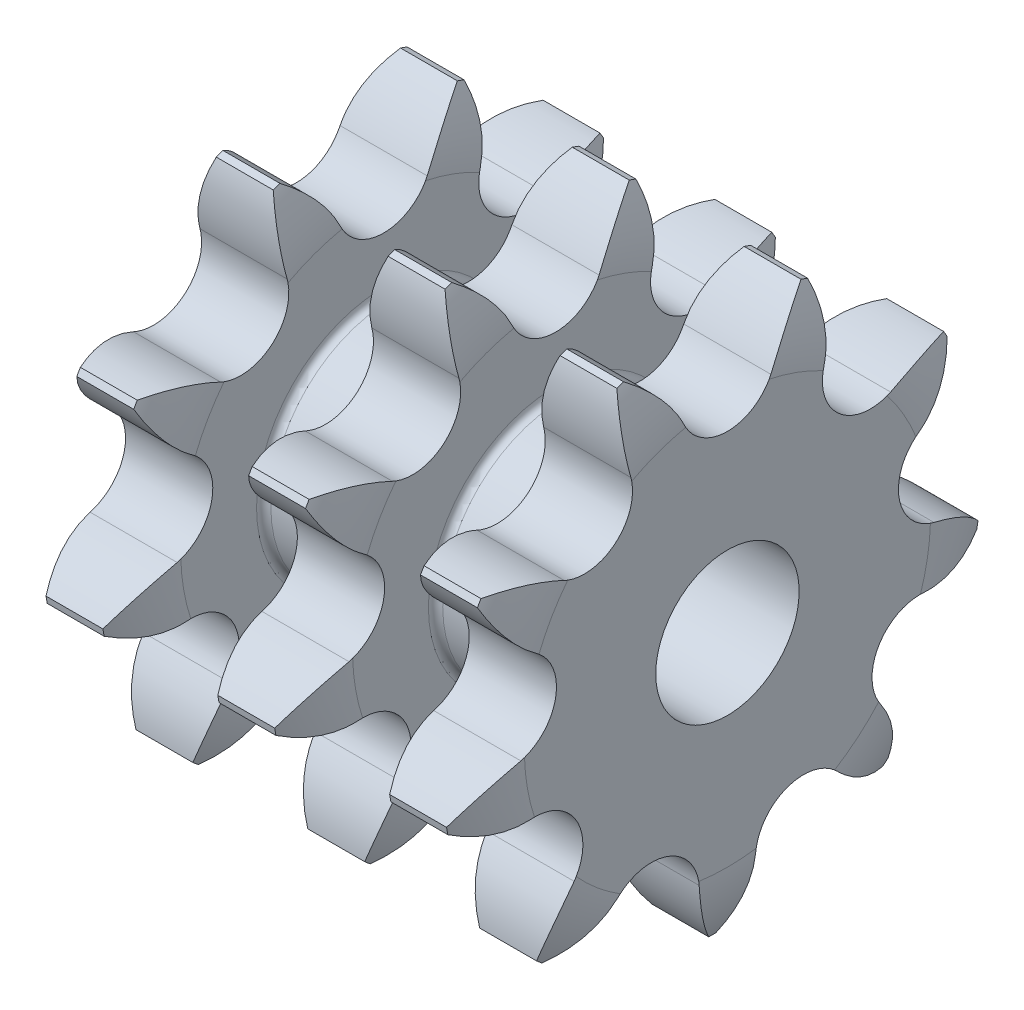
SolidWorks part; units mm, degrees
ref_plane "Plane1" through (0, 0, 0) normal (0, 0, 1) x (1, 0, 0)
ref_plane "Plane2" through (0, 0, 0) normal (0, 1, 0) x (1, 0, 0)
ref_plane "Plane3" through (0, 0, 0) normal (1, 0, 0) x (0, 0, -1)
sketch "Clipboard" plane through (0, 0, 0) normal (0, 1, 0) x (1, 0, 0)
  line L0 (0, 0) -> (12.5436, -1.9867)
  line L1 (-15, 0) -> (100, 0) construction
  line L2 (0, 0) -> (-0.8416, 0.9512)
  line L3 (0, 0) -> (-11.863, 4.5341)
  line L4 (0, 0) -> (3.0618, 0.4849)
  line L5 (0, 0) -> (-2.8109, -1.0484)
  line L6 (0, 0) -> (-29.8924, -20.1685)
  line L7 (-0.8416, 0.9512) -> (36.5829, 8.906)
  line L8 (-76.2, 38.1) -> (-75.2, 38.1)
  line L9 (-73.4321, 41.7084) -> (-72.837, 41.7846)
  line L10 (-73.4741, 12.9512) -> (-59.0941, 12.9512)
  circle A0 centre (0, 0) radius 3.975
  circle A1 centre (0, 0) radius 10.0465
  circle A2 centre (0, 0) radius 25
  dimension "Num_teeth" = 9
  dimension "Thickness" = 36.06
  dimension "Fillet_rad" = 0.6
sketch "BasProSke" plane through (0, 0, 0) normal (0, 1, 0) x (1, 0, 0)
  line L0 (-10, 0) -> (60, 0) construction
  line L1 (0, 0) -> (0, 16.9929)
  line L2 (0, 0) -> (36.06, 0)
  line L3 (36.06, 0) -> (36.06, 16.9929)
  line L4 (34.79, 22.5287) -> (1.27, 22.5287)
  arc A0 (0, 16.9929) -> (1.27, 22.5287) centre (12.7, 16.9929) cw
  arc A1 (36.06, 16.9929) -> (34.79, 22.5287) centre (23.36, 16.9929) ccw
  dimension "D1" = 12.7
  dimension "Thickness" = 36.06
  dimension "Diameter" = 45.0573
  dimension "G1" = 1.27
revolve "Base-Revolve" add sketch "BasProSke" angle 360 about L0
sketch "GrvSke" plane through (0, 0, 0) normal (0, 1, 0) x (1, 0, 0)
  line L0 (7.3, 16.9929) -> (7.3, 10.6465)
  line L1 (7.9, 10.0465) -> (13.78, 10.0465)
  line L2 (14.38, 10.6465) -> (14.38, 16.9929)
  line L3 (6.03, 22.5287) -> (15.65, 22.5287)
  line L4 (10.84, 0) -> (10.84, 52.07) construction
  line L5 (-10, 0) -> (60, 0) construction
  line L6 (0, 0) -> (35.56, 0) construction
  arc A0 (14.38, 16.9929) -> (15.65, 22.5287) centre (27.08, 16.9929) cw
  arc A1 (7.3, 16.9929) -> (6.03, 22.5287) centre (-5.4, 16.9929) ccw
  arc A2 (7.3, 10.6465) -> (7.9, 10.0465) centre (7.9, 10.6465) ccw
  arc A3 (13.78, 10.0465) -> (14.38, 10.6465) centre (13.78, 10.6465) ccw
  dimension "D1" = 12.7
  dimension "Diameter" = 45.0573
  dimension "Fillet_rad" = 0.6
  dimension "G1" = 1.27
  dimension "Grv_width" = 7.08
revolve "Groove" cut sketch "GrvSke" angle 360 about L6
pattern_linear "Grooves" count 2 spacing 14.38 along (1, 0, 0) of "Groove"
sketch "TooCutSke" plane through (0, 0, 0) normal (1, 0, 0) x (0, 0, -1)
  line L0 (0, 18.6059) -> (3.6386, 16.9092) construction
  line L1 (0, 0) -> (0, 107) construction
  line L2 (0, 18.6059) -> (-10, 18.6059) construction
  line L3 (0, 18.6059) -> (-3.6386, 16.9092) construction
  arc A0 (3.6386, 16.9092) -> (7.9748, 21.6037) centre (13.1494, 12.4742) cw
  arc A1 (3.6386, 16.9092) -> (-3.6386, 16.9092) centre (0, 18.6059) cw
  arc A2 (-3.6386, 16.9092) -> (-7.9748, 21.6037) centre (-13.1494, 12.4742) ccw
  arc A3 (7.9748, 21.6037) -> (-7.9748, 21.6037) centre (0, 0) ccw
extrude "ToothCut" cut sketch "TooCutSke" along normal through all
pattern_circular "TeethCuts" count 9 every 40 about axis through (-10, 0, 0) along (1, 0, 0) of "ToothCut"
sketch "HubNeaOneSke" plane through (0, 0, 0) normal (-1, 0, 0) x (0, 0, 1)
  circle A0 centre (0, 0) radius 10.0465
  dimension "Diameter" = 20.093
extrude "HubNearOne" [suppressed] add sketch "HubNeaOneSke" along normal blind 2.2005
fillet "HubNearOneFillet" [suppressed] radius 0.6
sketch "HubNeaBotSke" plane through (0, 0, 0) normal (-1, 0, 0) x (0, 0, 1)
  circle A0 centre (0, 0) radius 10.0465
  dimension "Diameter" = 20.093
extrude "HubNearBoth" [suppressed] add sketch "HubNeaBotSke" along normal blind 1.1003
fillet "HubNearBothFillet" [suppressed] radius 0.6
ref_plane "FarPln" through (36.06, 0, 0) normal (1, 0, 0) x (0, 0, -1)
sketch "HubFarSke" plane through (36.06, 0, 0) normal (1, 0, 0) x (0, 0, -1)
  circle A0 centre (0, 0) radius 10.0465
  dimension "Diameter" = 20.093
extrude "HubFar" [suppressed] add sketch "HubFarSke" along normal blind 1.1003
fillet "HubFarFillet" [suppressed] radius 0.6
sketch "BorSke" plane through (0, 0, 0) normal (1, 0, 0) x (0, 0, -1)
  circle A0 centre (0, 0) radius 6
  dimension "Diameter" = 12
extrude "Bore" cut sketch "BorSke" along normal mid plane 76.521
sketch "KeySke" plane through (0, 0, 0) normal (1, 0, 0) x (0, 0, -1)
  line L0 (-1, 0) -> (-1, 7)
  line L1 (-1, 7) -> (1, 7)
  line L2 (1, 7) -> (1, 0)
  line L3 (0, 0) -> (0, 34) construction
  line L4 (-1, 0) -> (1, 0)
  dimension "Offset" = 7
  dimension "Width" = 2
extrude "Keyway" [suppressed] cut sketch "KeySke" along normal mid plane 76.521
pattern_circular "Keyway2" [suppressed] count 2 every 90 about axis through (-10, 0, 0) along (1, 0, 0) reverse direction yes
equation "' \"Pitch@Clipboard\" = 12.7"
equation "' \"Num_strands@Clipboard\" = 3"
equation "' \"Num_teeth@Clipboard\" = 9"
equation "' \"Hub_dia@Clipboard\" = 50"
equation "' \"Overall_len@Clipboard\" = 3"
equation "' \"Diameter@BorSke\" = 12"
equation "' \"T_dim@Clipboard\" = 1"
equation "' \"Width@KeySke\" = 2"
equation "' \"Dr@Clipboard\" = 7.95"
equation "' \"Face_width@Clipboard\" = 7.3"
equation "' \"Side_radius@Clipboard\" = 12.7"
equation "' \"Side_relief@Clipboard\" = 1.27"
equation "' \"Transv_pitch@Clipboard\" = 14.38"
equation "' \"Show_teeth@Clipboard\" = 9"
equation "' \"Fillet_rad@Clipboard\" = 0.6"
equation "' \"Plate_wid@Clipboard\" = 12"
equation "\"Num_teeth@Clipboard\" = int( \"Num_teeth@Clipboard\" )"
equation "\"Num_teeth@Clipboard\" = ((sgn( \"Num_teeth@Clipboard\" - 5.0)+1)*( \"Num_teeth@Clipboard\" - 5.0))/2 +5.0"
equation "\"Num_teeth@Clipboard\" = ((sgn( \"Num_teeth@Clipboard\" - 200.0)-1)*( \"Num_teeth@Clipboard\" - 200.0))/-2 +200.0"
equation "\"MHD@Clipboard\" = \"Pitch@Clipboard\" * (1.0 / tan(3.14159265 / \"Num_teeth@Clipboard\" )) - 1.05 * \"Plate_wid@Clipboard\" - 2.0 * \"Fillet_rad@Clipboard\" - 1.0"
equation "\"Thickness@Clipboard\"  = \"Face_width@Clipboard\" + (\"Num_strands@Clipboard\" - 1) * \"Transv_pitch@Clipboard\""
equation "\"OAL@Clipboard\" = \"Thickness@Clipboard\" + 2 * \"Fillet_rad@Clipboard\" + 1"
equation "\"MHD@Clipboard\" = ((sgn( \"MHD@Clipboard\" - \"Hub_dia@Clipboard\" )-1)*( \"MHD@Clipboard\" - \"Hub_dia@Clipboard\" ))/-2+ \"Hub_dia@Clipboard\""
equation "\"OAL@Clipboard\" = ((sgn( \"OAL@Clipboard\" - \"Overall_len@Clipboard\" )+1)*( \"OAL@Clipboard\" - \"Overall_len@Clipboard\" ))/2 + \"Overall_len@Clipboard\" + 0.0005"
equation "\"Num_teeth@TeethCuts\" = int( \"Show_teeth@Clipboard\" ) + 1"
equation "\"Num_teeth@TeethCuts\" = ((sgn( \"Num_teeth@TeethCuts\" - \"Num_teeth@Clipboard\" )-1)*( \"Num_teeth@TeethCuts\" - \"Num_teeth@Clipboard\" ))/-2+ \"Num_teeth@Clipboard\""
equation "\"Num_teeth@TeethCuts\" = ((sgn( \"Num_teeth@TeethCuts\" - 2.0)+1)*( \"Num_teeth@TeethCuts\" - 2.0))/2 +2.0"
equation "\"Angle@TeethCuts\" = 360.0 / \"Num_teeth@Clipboard\""
equation "\"Seat_radius@TooCutSke\" = ( \"Pitch@Clipboard\" / 2.0) / sin(3.14159265 / \"Num_teeth@Clipboard\" ) - \"Dr@Clipboard\" / 2.0 + \"Dr@Clipboard\" * 0.505"
equation "\"R1@TooCutSke\"  = \"Dr@Clipboard\" * 0.505"
equation "\"X@TooCutSke\" = 140.0 - (90.0 / \"Num_teeth@Clipboard\")"
equation "\"R2@TooCutSke\" = 0.12 * \"Dr@Clipboard\" * ( \"Num_teeth@Clipboard\" + 2.0)"
equation "\"Overcut@TooCutSke\" = 0.5 + 0.625 * \"Pitch@Clipboard\" - 0.5 * \"Dr@Clipboard\"  +  \"Pitch@Clipboard\" / 2.0 / sin(3.14159265 / \"Num_teeth@Clipboard\" )"
equation "\"Diameter@BasProSke\" = 2.0 * ( 0.625 * \"Pitch@Clipboard\" - 0.5 * \"Dr@Clipboard\"  +  \"Pitch@Clipboard\" / 2.0 / sin(3.14159265 / \"Num_teeth@Clipboard\" ))"
equation "\"Thickness@BasProSke\"  = \"Thickness@Clipboard\""
equation "\"G1@BasProSke\" =  \"Side_relief@Clipboard\""
equation "\"G2@BasProSke\" =  \"Side_relief@Clipboard\""
equation "\"D1@BasProSke\" =  \"Side_radius@Clipboard\""
equation "\"Diameter@GrvSke\" = \"Diameter@BasProSke\""
equation "\"G1@GrvSke\" = \"Side_relief@Clipboard\""
equation "\"D1@GrvSke\" = \"Side_radius@Clipboard\""
equation "\"Grv_diam@GrvSke\" =  \"Pitch@Clipboard\" * (1.0 / tan(3.14159265 / \"Num_teeth@Clipboard\" ))- 1.05 * \"Plate_wid@Clipboard\" - 2.0 * \"Fillet_rad@Clipboard\" - 1.0"
equation "\"Grv_width@GrvSke\" =  \"Transv_pitch@Clipboard\" - \"Face_width@Clipboard\""
equation "\"Offset@GrvSke\" = \"Grv_width@GrvSke\" / 2.0 + \"Face_width@Clipboard\""
equation "\"Fillet_rad@GrvSke\" = \"Fillet_rad@Clipboard\""
equation "\"Offset@Grooves\" = \"Transv_pitch@Clipboard\""
equation "\"Num_grvs@Grooves\" = \"Num_strands@Clipboard\""
equation "\"Num_grvs@Grooves\" = \"Num_grvs@Grooves\" - 1 * sgn( \"Num_grvs@Grooves\" -1)"
equation "\"Diameter@HubNeaOneSke\" = \"MHD@Clipboard\""
equation "\"Length@HubNearOne\" = \"OAL@Clipboard\" - \"Thickness@BasProSke\""
equation "\"Diameter@HubNeaBotSke\" = \"MHD@Clipboard\""
equation "\"Length@HubNearBoth\" = ( \"OAL@Clipboard\" - \"Thickness@BasProSke\" ) / 2.0"
equation "\"D1@HubNearOneFillet\" = \"Fillet_rad@Clipboard\""
equation "\"D1@HubNearBothFillet\" = \"Fillet_rad@Clipboard\""
equation "\"Thickness@FarPln\" = \"Thickness@BasProSke\""
equation "\"Diameter@HubFarSke\" = \"MHD@Clipboard\""
equation "\"Length@HubFar\" = ( \"OAL@Clipboard\" - \"Thickness@BasProSke\" ) / 2.0"
equation "\"D1@HubFarFillet\" = \"Fillet_rad@Clipboard\""
equation "\"D1@Bore\" = \"OAL@Clipboard\" * 2.0"
equation "\"D1@Keyway\" = \"OAL@Clipboard\" * 2.0"
equation "\"Offset@KeySke\" = \"T_dim@Clipboard\" + \"Diameter@BorSke\" / 2.0"
